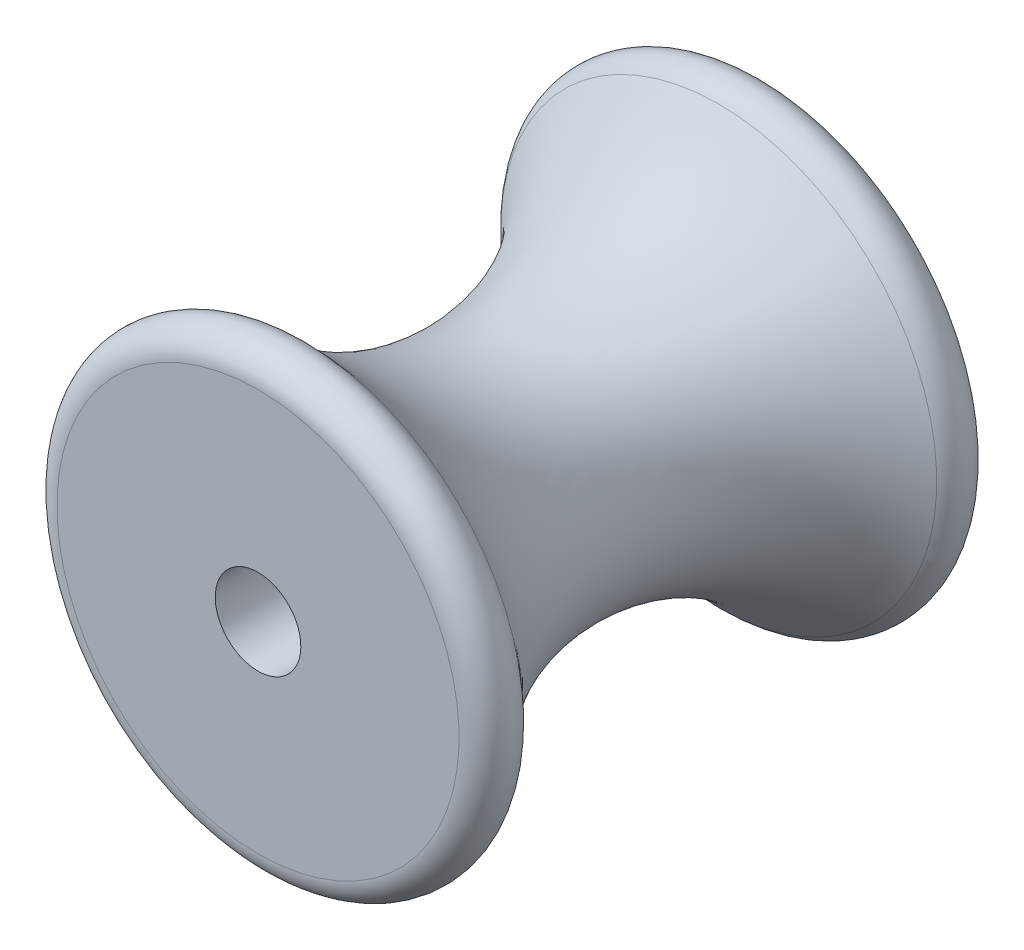
SolidWorks part; units mm, degrees
ref_plane "Front Plane" through (0, 0, 0) normal (0, 0, 1) x (1, 0, 0)
ref_plane "Top Plane" through (0, 0, 0) normal (0, 1, 0) x (1, 0, 0)
ref_plane "Right Plane" through (0, 0, 0) normal (1, 0, 0) x (0, 0, -1)
sketch "Sketch1" plane through (0, 0, 0) normal (1, 0, 0) x (0, 0, -1)
  line L0 (10, 0) -> (-10, 0) construction
  line L1 (10, 16.5) -> (10, -26.9006) construction
  line L2 (10, 1.6) -> (-10, 1.6) construction
  line L4 (0, 9.3697) -> (0, -9.3697) construction
  line L5 (10, 1.6) -> (10, 14.5) construction
  line L6 (-10, 1.6) -> (-10, 14.5) construction
  line L7 (9.5, 1.6) -> (9.5, 11.3775)
  line L8 (-9.5, 1.6) -> (-9.5, 11.3775)
  line L9 (9.5, 1.6) -> (-9.5, 1.6)
  circle A0 centre (0, 14.5) radius 10 construction
  arc A1 (9.5, 11.3775) -> (-9.5, 11.3775) centre (0, 14.5) cw
  point P2 (0, 0)
  dimension "D1" = 1
revolve "Revolve1" add sketch "Sketch1" angle 360 about L0 region at (0, 4.3273, 0)
fillet "Fillet1" radius 1 2 edges at (0, 11.3775, 9.5) (0, 11.3775, -9.5)
